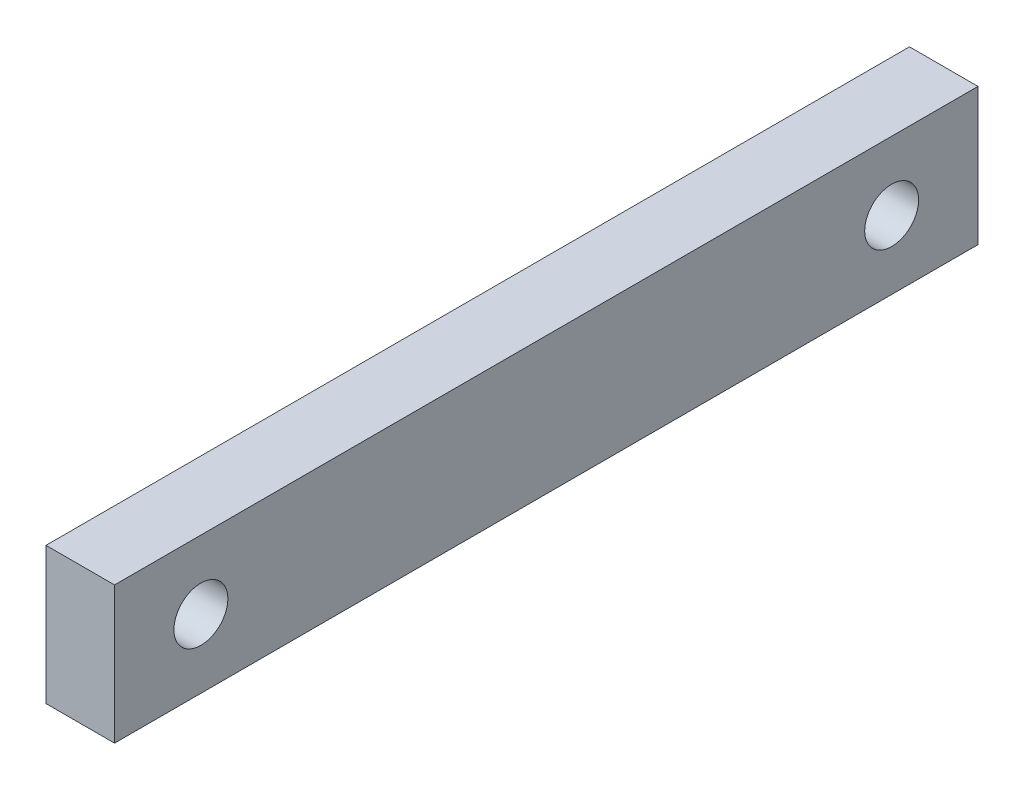
SolidWorks part; units mm, degrees
ref_plane "Front Plane" through (0, 0, 0) normal (0, 0, 1) x (1, 0, 0)
ref_plane "Top Plane" through (0, 0, 0) normal (0, 1, 0) x (1, 0, 0)
ref_plane "Right Plane" through (0, 0, 0) normal (1, 0, 0) x (0, 0, -1)
sketch "Sketch2" plane through (0, 0, 0) normal (0, 0, 1) x (1, 0, 0)
  line L1 (-3.175, -6.35) -> (3.175, -6.35)
  line L2 (-3.175, -6.35) -> (-3.175, 6.35)
  line L3 (-3.175, 6.35) -> (3.175, 6.35)
  line L4 (3.175, -6.35) -> (3.175, 6.35)
  line L5 (-3.175, -6.35) -> (3.175, 6.35) construction
  line L6 (-3.175, 6.35) -> (3.175, -6.35) construction
  point P0 (0, 0)
  dimension "D1" = 6.35
  dimension "D2" = 12.7
extrude "Boss-Extrude1" add sketch "Sketch2" along normal blind 40 and the other way blind 40
sketch "Sketch4" plane through (3.175, 0, 0) normal (1, 0, 0) x (0, 0, -1)
  line L0 (0, 0) -> (0, -6.35) construction
  line L1 (40, -6.35) -> (-40, -6.35) construction
  line L2 (-40, -6.35) -> (-40, 6.35) construction
  circle A0 centre (-32, 0) radius 2.5
  circle A1 centre (32, 0) radius 2.5
  dimension "D1" = 5
  dimension "D2" = 8
extrude "Cut-Extrude1" cut sketch "Sketch4" against normal through all
